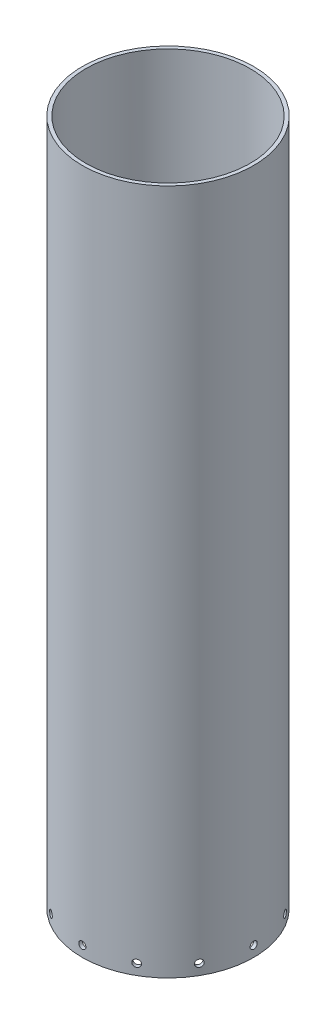
SolidWorks part; units mm, degrees
material "Polycarbonate"
ref_plane "Front Plane" through (0, 0, 0) normal (0, 0, 1) x (1, 0, 0)
ref_plane "Top Plane" through (0, 0, 0) normal (0, 1, 0) x (1, 0, 0)
ref_plane "Right Plane" through (0, 0, 0) normal (1, 0, 0) x (0, 0, -1)
sketch "Sketch2" plane through (0, 0, 0) normal (0, 1, 0) x (1, 0, 0)
  circle A0 centre (0, 0) radius 73.025
  circle A1 centre (0, 0) radius 76.2
  dimension "D1" = 146.05
  dimension "D2" = 152.4
extrude "Boss-Extrude1" add sketch "Sketch2" along normal blind 609.6
sketch "Sketch3" plane through (0, 0, 0) normal (0, 0, 1) x (1, 0, 0)
  line L0 (0, 0) -> (0, 235.745) construction
  line L1 (-76.2, 0) -> (76.2, 0) construction
  circle A0 centre (0, 9.525) radius 3.175
  dimension "D1" = 9.525
extrude "Cut-Extrude1" cut sketch "Sketch3" against normal through all
ref_axis "Axis1" through (0, 0, 0) along (0, 1, 0)
pattern_circular "CirPattern1" count 12 over 360 about axis through (0, 0, 0) along (0, 1, 0) of "Cut-Extrude1"
